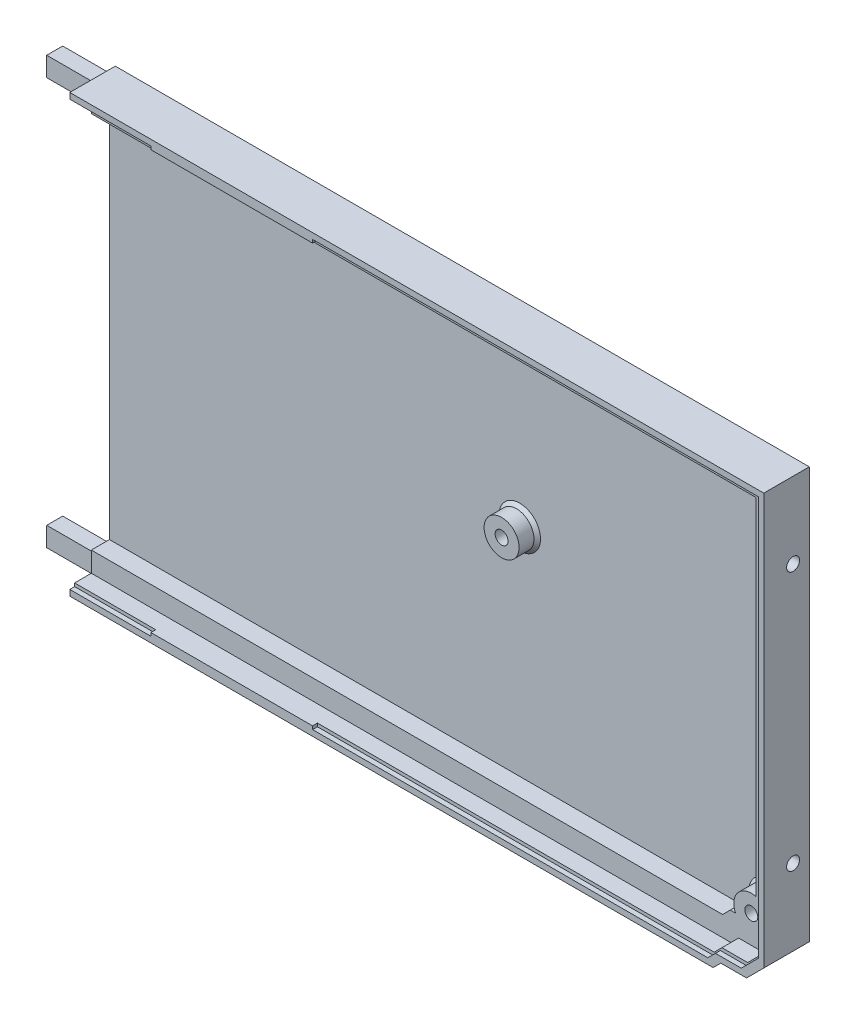
SolidWorks part; units mm, degrees
ref_plane "Přední rovina" through (0, 0, 0) normal (0, 0, 1) x (1, 0, 0)
ref_plane "Horní rovina" through (0, 0, 0) normal (0, 1, 0) x (1, 0, 0)
ref_plane "Pravá rovina" through (0, 0, 0) normal (1, 0, 0) x (0, 0, -1)
sketch "Skica3" plane through (0, 0, 0) normal (0, 0, 1) x (1, 0, 0)
  line L0 (0, 0) -> (415.1053, 0) construction
  line L1 (415.1053, 0) -> (416.6927, -1.5875) construction
  line L2 (416.6927, -1.5875) -> (416.6927, -119.8485) construction
  line L3 (0, 0) -> (-1.5875, -1.5875) construction
  line L4 (-1.5875, -1.5875) -> (-1.5875, -119.8485) construction
  line L5 (-1.5875, -119.8485) -> (0.7934, -122.2292) construction
  line L6 (0.7934, -122.2292) -> (8.7304, -122.2292) construction
  line L7 (8.7304, -122.2292) -> (11.1113, -124.61) construction
  line L8 (11.1113, -124.61) -> (403.9933, -124.61) construction
  line L9 (403.9933, -124.61) -> (406.3744, -122.2294) construction
  line L10 (406.3744, -122.2294) -> (414.3114, -122.2294) construction
  line L11 (416.6927, -119.8485) -> (414.3114, -122.2294) construction
  line L12 (2.4125, -4) -> (412.6927, -4)
  line L13 (412.6927, -4) -> (412.6927, -4)
  line L14 (412.6927, -4) -> (412.6927, -118.1914)
  line L15 (412.6927, -118.1914) -> (412.6547, -118.2294)
  line L16 (404.7177, -118.2294) -> (412.6547, -118.2294)
  line L17 (402.3367, -120.61) -> (404.7177, -118.2294)
  line L18 (12.7681, -120.61) -> (402.3367, -120.61)
  line L19 (10.3872, -118.2292) -> (12.7681, -120.61)
  line L20 (2.4502, -118.2292) -> (10.3872, -118.2292)
  line L21 (2.4125, -118.1915) -> (2.4502, -118.2292)
  line L22 (2.4125, -4) -> (2.4125, -118.1915)
  line L23 (2.4125, -4) -> (2.4125, -4)
  line L24 (-1.5875, -119.8485) -> (415.1053, 0) construction
  line L26 (0, 0) -> (416.6927, -119.8485) construction
  dimension "D1" = 135
  dimension "D2" = 135
  dimension "D3" = 4
  dimension "D4" = 2.245
  dimension "D5" = 2.245
  dimension "D6" = 118.261
  dimension "D7" = 118.261
  dimension "D8" = 3.367
  dimension "D9" = 7.937
  dimension "D10" = 3.367
  dimension "D11" = 392.882
  dimension "D12" = 3.367
  dimension "D13" = 7.937
  dimension "D14" = 3.3674
extrude "Přidat vysunutím1" add sketch "Skica3" along normal blind 5.6
shell "Skořepina1" thickness 1.8 removed face at (207.5525, -95.852, 5.6) outward yes
sketch "Skica7" plane through (0, 0, 5.6) normal (0, 0, 1) x (1, 0, 0)
  line L20 (-6.5875, 5) -> (-6.5875, -121.9196)
  line L21 (-6.5875, -121.9196) -> (-1.2775, -127.2292)
  line L22 (-1.2775, -127.2292) -> (6.6595, -127.2292)
  line L23 (6.6595, -127.2292) -> (9.0403, -129.61)
  line L24 (9.0403, -129.61) -> (406.0641, -129.61)
  line L25 (406.0641, -129.61) -> (408.4452, -127.2294)
  line L26 (408.4452, -127.2294) -> (416.3822, -127.2294)
  line L27 (416.3822, -127.2294) -> (421.6927, -121.9198)
  line L28 (421.6927, -121.9198) -> (421.6927, 5)
  line L29 (421.6927, 5) -> (-6.5875, 5)
  line L30 (-6.5875, 5) -> (-6.5875, -121.9196)
  line L31 (-6.5875, -121.9196) -> (-1.2775, -127.2292)
  line L32 (-1.2775, -127.2292) -> (6.6595, -127.2292)
  line L33 (6.6595, -127.2292) -> (9.0403, -129.61)
  line L34 (9.0403, -129.61) -> (406.0641, -129.61)
  line L35 (406.0641, -129.61) -> (408.4452, -127.2294)
  line L36 (408.4452, -127.2294) -> (416.3822, -127.2294)
  line L37 (416.3822, -127.2294) -> (421.6927, -121.9198)
  line L38 (421.6927, -121.9198) -> (421.6927, 5)
  line L39 (421.6927, 5) -> (-6.5875, 5)
  line L40 (-3.7875, 2.2) -> (-3.7875, -120.7598)
  line L41 (-3.7875, -120.7598) -> (-0.1178, -124.4292)
  line L42 (-0.1178, -124.4292) -> (7.8192, -124.4292)
  line L43 (7.8192, -124.4292) -> (10.2001, -126.81)
  line L44 (10.2001, -126.81) -> (404.9045, -126.81)
  line L45 (404.9045, -126.81) -> (407.2855, -124.4294)
  line L46 (407.2855, -124.4294) -> (415.2225, -124.4294)
  line L47 (415.2225, -124.4294) -> (418.8927, -120.7598)
  line L48 (418.8927, -120.7598) -> (418.8927, 2.2)
  line L49 (418.8927, 2.2) -> (-3.7875, 2.2)
  line L50 (-3.7875, 2.2) -> (-3.7875, -120.7598)
  line L51 (-3.7875, -120.7598) -> (-0.1178, -124.4292)
  line L52 (-0.1178, -124.4292) -> (7.8192, -124.4292)
  line L53 (7.8192, -124.4292) -> (10.2001, -126.81)
  line L54 (10.2001, -126.81) -> (404.9045, -126.81)
  line L55 (404.9045, -126.81) -> (407.2855, -124.4294)
  line L56 (407.2855, -124.4294) -> (415.2225, -124.4294)
  line L57 (415.2225, -124.4294) -> (418.8927, -120.7598)
  line L58 (418.8927, -120.7598) -> (418.8927, 2.2)
  line L59 (418.8927, 2.2) -> (-3.7875, 2.2)
  dimension "D2" = 4.4
  dimension "D1" = 7.2
extrude "Přidat vysunutím3" add sketch "Skica7" along normal blind 5.15 separate body
sketch "Skica8" plane through (0, 0, 5.6) normal (0, 0, -1) x (-1, 0, 0)
  line L0 (-421.6927, 5) -> (6.5875, 5)
  line L1 (6.5875, 5) -> (6.5875, -121.9196)
  line L2 (6.5875, 5) -> (6.5875, -121.9196) construction
  line L3 (6.5875, -121.9196) -> (1.2775, -127.2292)
  line L4 (1.2775, -127.2292) -> (-6.6595, -127.2292)
  line L5 (-6.6595, -127.2292) -> (-9.0403, -129.61)
  line L6 (-9.0403, -129.61) -> (-406.0641, -129.61)
  line L7 (-406.0641, -129.61) -> (-408.4452, -127.2294)
  line L8 (-408.4452, -127.2294) -> (-416.3822, -127.2294)
  line L9 (-416.3822, -127.2294) -> (-421.6927, -121.9198)
  line L10 (-421.6927, -121.9198) -> (-421.6927, 5)
  line L11 (-0.6125, -2.2) -> (-0.6125, -118.9371)
  line L12 (-414.4927, -2.2) -> (-0.6125, -2.2) construction
  line L13 (-0.6125, -2.2) -> (-0.6125, -118.9371) construction
  line L14 (-0.6125, -118.9371) -> (-1.7047, -120.0292)
  line L15 (-1.7047, -120.0292) -> (-9.6417, -120.0292)
  line L16 (-9.6417, -120.0292) -> (-12.0226, -122.41)
  line L17 (-12.0226, -122.41) -> (-403.0822, -122.41)
  line L18 (-403.0822, -122.41) -> (-405.4632, -120.0294)
  line L19 (-405.4632, -120.0294) -> (-413.4002, -120.0294) construction
  line L20 (-405.4632, -120.0294) -> (-413.4002, -120.0294)
  line L21 (-413.4002, -120.0294) -> (-414.4927, -118.9371) construction
  line L22 (-413.4002, -120.0294) -> (-414.4927, -118.9371)
  line L23 (-414.4927, -118.9371) -> (-414.4927, -2.2)
  line L24 (-414.4927, -2.2) -> (-0.6125, -2.2)
extrude "Přidat vysunutím4" add sketch "Skica8" along normal up to surface (7.4 mm away) up to face at (207.5525, -96.7211, -1.8)
sketch "Skica11" plane through (0, 0, 10.75) normal (0, 0, 1) x (1, 0, 0)
  line L0 (207.5526, 3.195) -> (207.5526, 5) construction
  line L1 (421.6927, 5) -> (-6.5875, 5) construction
  line L2 (207.5522, -127.805) -> (207.5522, -129.61) construction
  line L3 (9.0403, -129.61) -> (406.0641, -129.61) construction
  line L4 (-4.9474, -58.4598) -> (-6.5875, -58.4598) construction
  line L5 (-6.5875, 5) -> (-6.5875, -121.9196) construction
  line L6 (420.0526, -58.4599) -> (421.6927, -58.4599) construction
  line L7 (421.6927, -121.9198) -> (421.6927, 5) construction
  line L8 (404.9045, -126.81) -> (407.2855, -124.4294) construction
  line L9 (415.2225, -124.4294) -> (418.8927, -120.7598) construction
  line L10 (7.8192, -124.4292) -> (10.2001, -126.81) construction
  line L11 (-3.7875, -120.7598) -> (-0.1178, -124.4292) construction
  line L13 (407.2855, -124.4294) -> (415.2225, -124.4294) construction
  line L14 (-0.1178, -124.4292) -> (7.8192, -124.4292) construction
  line L30 (420.0526, 3.195) -> (-4.9474, 3.195)
  line L31 (-4.9474, 3.195) -> (-4.9474, -120.1146)
  line L32 (-4.9474, -120.1146) -> (-0.24, -124.8217)
  line L33 (-0.24, -124.8217) -> (7.697, -124.8217)
  line L34 (7.697, -124.8217) -> (10.6804, -127.805)
  line L35 (10.6804, -127.805) -> (404.4241, -127.805)
  line L36 (404.4241, -127.805) -> (406.8051, -125.4244)
  line L37 (406.8051, -125.4244) -> (414.7421, -125.4244)
  line L38 (414.7421, -125.4244) -> (420.0526, -120.1148)
  line L39 (420.0526, -120.1148) -> (420.0526, 3.195)
  line L45 (421.6927, 5) -> (-6.5875, 5)
  line L46 (-6.5875, 5) -> (-6.5875, -121.9196)
  line L47 (-6.5875, -121.9196) -> (-1.2775, -127.2292)
  line L48 (-1.2775, -127.2292) -> (6.6595, -127.2292)
  line L49 (6.6595, -127.2292) -> (9.0403, -129.61)
  line L50 (9.0403, -129.61) -> (406.0641, -129.61)
  line L51 (406.0641, -129.61) -> (408.4452, -127.2294)
  line L52 (408.4452, -127.2294) -> (416.3822, -127.2294)
  line L53 (416.3822, -127.2294) -> (421.6927, -121.9198)
  line L54 (421.6927, -121.9198) -> (421.6927, 5)
  line L55 (421.6927, 5) -> (-6.5875, 5)
  line L56 (-6.5875, 5) -> (-6.5875, -121.9196)
  line L57 (-6.5875, -121.9196) -> (-1.2775, -127.2292)
  line L58 (-1.2775, -127.2292) -> (6.6595, -127.2292)
  line L59 (6.6595, -127.2292) -> (9.0403, -129.61)
  line L60 (9.0403, -129.61) -> (406.0641, -129.61)
  line L61 (406.0641, -129.61) -> (408.4452, -127.2294)
  line L62 (408.4452, -127.2294) -> (416.3822, -127.2294)
  line L63 (416.3822, -127.2294) -> (421.6927, -121.9198)
  line L64 (421.6927, -121.9198) -> (421.6927, 5)
  point P0 (207.5523, -63.11)
  point P2 (207.5523, -63.11)
  dimension "D1" = 131
  dimension "D2" = 425
  dimension "D3" = 0
extrude "Přidat vysunutím5" add sketch "Skica11" along normal blind 1.5
sketch "Skica14" plane through (0, 0, 10.75) normal (0, 0, 1) x (1, 0, 0)
  line L0 (418.8927, 2.2) -> (-3.7875, 2.2) construction
  line L1 (182.5326, 2.2) -> (132.6326, 2.2)
  line L2 (182.5326, 2.2) -> (182.5326, 3.195)
  line L3 (182.5326, 3.195) -> (132.6326, 3.195)
  line L4 (132.6326, 2.2) -> (132.6326, 3.195)
  line L5 (420.0526, 3.195) -> (-4.9474, 3.195) construction
  line L6 (418.8927, 2.2) -> (-3.7875, 2.2) construction
  line L7 (232.5726, 2.2) -> (282.4726, 2.2)
  line L8 (232.5726, 2.2) -> (232.5726, 3.195)
  line L9 (232.5726, 3.195) -> (282.4726, 3.195)
  line L10 (282.4726, 2.2) -> (282.4726, 3.195)
  line L11 (207.5526, 3.195) -> (207.5522, -127.805) construction
  line L12 (10.6804, -127.805) -> (404.4241, -127.805) construction
  line L13 (10.2001, -126.81) -> (404.9045, -126.81) construction
  line L14 (232.5722, -126.81) -> (282.4722, -126.81)
  line L15 (232.5722, -126.81) -> (232.5722, -127.805)
  line L16 (232.5722, -127.805) -> (282.4722, -127.805)
  line L17 (282.4722, -126.81) -> (282.4722, -127.805)
  line L18 (10.6804, -127.805) -> (404.4241, -127.805) construction
  line L20 (182.5322, -126.81) -> (132.6322, -126.81)
  line L21 (182.5322, -126.81) -> (182.5322, -127.805)
  line L22 (182.5322, -127.805) -> (132.6322, -127.805)
  line L23 (132.6322, -126.81) -> (132.6322, -127.805)
  dimension "D1" = 49.9
  dimension "D2" = 49.9
  dimension "D3" = 25.02
  dimension "D4" = 25.02
  dimension "D5" = 49.9
  dimension "D6" = 49.9
  dimension "D7" = 25.02
  dimension "D8" = 25.02
extrude "Přidat vysunutím6" add sketch "Skica14" along normal up to surface (1.5 mm away) up to face at (207.5524, -100.1977, 12.25)
sketch "Skica15" plane through (0, 0, 0) normal (0, 0, 1) x (1, 0, 0)
  line L1 (34.9015, 4.5) -> (37.9015, 4.5)
  line L2 (34.9015, 4.5) -> (34.9015, -4.5)
  line L3 (34.9015, -4.5) -> (37.9015, -4.5)
  line L4 (37.9015, 4.5) -> (37.9015, -4.5)
  line L5 (34.9015, 4.5) -> (37.9015, -4.5) construction
  line L6 (34.9015, -4.5) -> (37.9015, 4.5) construction
  line L20 (-1.5875, 0) -> (-1.5875, -119.8485)
  line L21 (-1.5875, -119.8485) -> (0.7934, -122.2292)
  line L22 (0.7934, -122.2292) -> (8.7304, -122.2292)
  line L23 (8.7304, -122.2292) -> (11.1113, -124.61)
  line L24 (11.1113, -124.61) -> (403.9933, -124.61)
  line L25 (403.9933, -124.61) -> (406.3744, -122.2294)
  line L26 (406.3744, -122.2294) -> (414.3114, -122.2294)
  line L27 (414.3114, -122.2294) -> (416.6927, -119.8485)
  line L28 (416.6927, -119.8485) -> (416.6927, 0)
  line L29 (416.6927, 0) -> (-1.5875, 0)
  line L30 (-1.5875, 0) -> (-1.5875, -119.8485) construction
  line L31 (-1.5875, -119.8485) -> (0.7934, -122.2292) construction
  line L32 (0.7934, -122.2292) -> (8.7304, -122.2292) construction
  line L33 (8.7304, -122.2292) -> (11.1113, -124.61) construction
  line L34 (11.1113, -124.61) -> (403.9933, -124.61) construction
  line L35 (403.9933, -124.61) -> (406.3744, -122.2294) construction
  line L36 (406.3744, -122.2294) -> (414.3114, -122.2294) construction
  line L37 (414.3114, -122.2294) -> (416.6927, -119.8485) construction
  line L38 (416.6927, -119.8485) -> (416.6927, 0) construction
  line L39 (416.6927, 0) -> (-1.5875, 0) construction
  circle A0 centre (3.9685, -115.9542) radius 5.4
  circle A1 centre (33.4915, -69.051) radius 5.4
  circle A2 centre (411.1977, -115.8794) radius 5.4
  circle A3 centre (334.1477, -53.972) radius 5.4
  point P2 (-1.4315, -115.9542)
  point P3 (3.9685, -121.3542)
  point P4 (28.0915, -69.051)
  point P8 (33.4915, -74.451)
  point P12 (411.1977, -121.2794)
  point P13 (416.5977, -115.8794)
  point P17 (334.1477, -48.572)
  point P19 (339.5477, -53.972)
  point P21 (36.4015, 0)
  point P23 (36.4015, 0)
  dimension "D2" = 0.156
  dimension "D4" = 10.8
  dimension "D7" = 10.8
  dimension "D10" = 10.8
  dimension "D13" = 10.8
  dimension "D3" = 0.875
  dimension "D5" = 29.679
  dimension "D6" = 50.159
  dimension "D8" = 0.095
  dimension "D9" = 0.95
  dimension "D11" = 77.145
  dimension "D12" = 48.572
  dimension "D14" = 37.989
  dimension "D15" = 9
  dimension "D16" = 3
  dimension "D1" = 4
extrude "Přidat vysunutím7" add sketch "Skica15" along normal blind 5.6
sketch "Skica16" plane through (0, 0, 5.6) normal (0, 0, 1) x (1, 0, 0)
  circle A0 centre (3.9685, -115.9542) radius 2
  circle A1 centre (33.4915, -69.051) radius 2
  circle A2 centre (334.1477, -53.972) radius 2
  circle A3 centre (411.1977, -115.8794) radius 2
  dimension "D1" = 4
  dimension "D2" = 4
  dimension "D3" = 4
  dimension "D4" = 4
extrude "Odebrat vysunutím1" cut sketch "Skica16" against normal blind 5.75
chamfer "Zkosení1" distance 1 angle 45 4 edges at (407.0694, -112.3984, 0) (8.0492, -112.4175, 0) (38.8915, -69.051, 0) (339.5477, -53.972, 0)
sketch "Skica17" plane through (0, 0, 5.6) normal (0, 0, 1) x (1, 0, 0)
  line L0 (34.9015, -4.5) -> (37.9015, -4.5) construction
  line L1 (24.4015, -11.2) -> (48.4015, -11.2)
  line L2 (24.4015, -11.2) -> (24.4015, 2.2)
  line L3 (24.4015, 2.2) -> (48.4015, 2.2)
  line L4 (48.4015, -11.2) -> (48.4015, 2.2)
  line L5 (24.4015, -11.2) -> (48.4015, 2.2) construction
  line L6 (24.4015, 2.2) -> (48.4015, -11.2) construction
  line L7 (418.8927, 2.2) -> (-3.7875, 2.2) construction
  point P0 (36.4015, -4.5)
  dimension "D1" = 24
extrude "Odebrat vysunutím2" cut sketch "Skica17" against normal blind 1.6
sketch "Skica18" plane through (0, -4.5, 0) normal (0, -1, 0) x (1, 0, 0)
  line L0 (33.6515, 4) -> (39.1515, 4) construction
  line L1 (37.9015, 4) -> (34.9015, 4) construction
  line L2 (37.9015, 4) -> (48.4015, 4) construction
  line L3 (33.6515, 7.5) -> (39.1515, 7.5)
  line L4 (33.6515, 0.5) -> (39.1515, 0.5)
  arc A0 (33.6515, 7.5) -> (33.6515, 0.5) centre (33.6515, 4) ccw
  arc A1 (39.1515, 0.5) -> (39.1515, 7.5) centre (39.1515, 4) ccw
  point P6 (36.4015, 4)
  point P11 (30.1515, 4)
  point P12 (42.6515, 4)
  dimension "D1" = 12.5
  dimension "D2" = 7
extrude "Odebrat vysunutím3" cut sketch "Skica18" against normal up to surface (9.5 mm away) up to face at (207.5526, 5, 5.225)
sketch "Skica23" plane through (-6.5875, 0, 0) normal (-1, 0, 0) x (0, 0, 1)
  line L2 (-1.8, 5) -> (-1.8, -121.9196) construction
  line L4 (-1.8, -58.4598) -> (12.25, -58.4598) construction
  line L5 (12.25, 5) -> (12.25, -121.9196) construction
  circle A0 centre (3.2, -18.4598) radius 2
  circle A1 centre (3.2, -98.4598) radius 2
  point P8 (-1.8, -58.4598)
  dimension "D2" = 4
  dimension "D3" = 4
  dimension "D1" = 40
  dimension "D4" = 5
extrude "Odebrat vysunutím4" cut sketch "Skica23" against normal blind 5.7
sketch "Skica24" plane through (421.6927, 0, 0) normal (1, 0, 0) x (0, 0, -1)
  line L0 (1.8, -58.4599) -> (-12.25, -58.4599) construction
  line L1 (1.8, -121.9198) -> (1.8, 5) construction
  line L2 (-12.25, -121.9198) -> (-12.25, 5) construction
  circle A0 centre (-3.2, -18.4599) radius 2
  circle A1 centre (-3.2, -98.4599) radius 2
  dimension "D1" = 4
  dimension "D2" = 4
  dimension "D3" = 40
  dimension "D4" = 5
extrude "Odebrat vysunutím5" cut sketch "Skica24" against normal blind 5.7
sketch "Skica25" plane through (0, 0, -1.8) normal (0, 0, -1) x (-1, 0, 0)
  line L0 (-421.6927, -121.9198) -> (-421.6927, 5) construction
  line L1 (-421.6927, 5) -> (6.5875, 5) construction
  line L2 (6.5875, 5) -> (6.5875, -121.9196) construction
  line L3 (-9.0403, -129.61) -> (-406.0641, -129.61) construction
  circle A0 centre (-401.6927, -15) radius 6.25
  circle A1 centre (-13.4125, -15) radius 6.25
  circle A2 centre (-388.4452, -109.61) radius 6.25
  circle A3 centre (-26.6595, -109.61) radius 6.25
  dimension "D1" = 12.5
  dimension "D2" = 12.5
  dimension "D3" = 12.5
  dimension "D4" = 12.5
  dimension "D5" = 20
  dimension "D6" = 20
  dimension "D7" = 20
  dimension "D8" = 20
  dimension "D9" = 20
  dimension "D10" = 20
  dimension "D11" = 20
  dimension "D12" = 20
extrude "Odebrat vysunutím6" cut sketch "Skica25" against normal blind 1.5
sketch "Skica26" plane through (0, 5, 0) normal (0, 1, 0) x (1, 0, 0)
  line L0 (421.6927, -12.25) -> (-6.5875, -12.25) construction
  line L1 (207.5526, -12.25) -> (-6.5875, -12.25)
  line L2 (207.5526, -12.25) -> (207.5526, 1.8)
  line L3 (207.5526, 1.8) -> (-6.5875, 1.8)
  line L4 (-6.5875, -12.25) -> (-6.5875, 1.8)
extrude "Odebrat vysunutím7" cut sketch "Skica26" against normal through all
sketch "Skica27" plane through (207.5526, 0, 0) normal (-1, 0, 0) x (0, 0, 1)
  line L0 (0, -4) -> (-1.8, -4) construction
  line L1 (-1.8, -129.61) -> (-1.8, 5) construction
  line L2 (-1.8, -4) -> (5.6, 5) construction
  line L3 (12.25, 5) -> (-1.8, 5) construction
  line L4 (5.6, 5) -> (5.6, 2.2) construction
  line L5 (-1.8, 5) -> (5.6, -4) construction
  line L6 (0, -120.61) -> (-1.8, -120.61) construction
  line L7 (-0.5667, -2.5) -> (4.3667, -2.5)
  line L8 (-0.5667, -2.5) -> (-0.5667, 3.5)
  line L9 (-0.5667, 3.5) -> (4.3667, 3.5)
  line L10 (4.3667, -2.5) -> (4.3667, 3.5)
  line L11 (-0.5667, -2.5) -> (4.3667, 3.5) construction
  line L12 (-0.5667, 3.5) -> (4.3667, -2.5) construction
  line L13 (5.6, -126.81) -> (5.6, -129.61) construction
  line L14 (12.25, -129.61) -> (-1.8, -129.61) construction
  line L15 (-1.8, -120.61) -> (5.6, -129.61) construction
  line L16 (-1.8, -129.61) -> (5.6, -120.61) construction
  line L17 (5.6, -120.61) -> (0, -120.61) construction
  line L18 (-0.5667, -128.11) -> (4.3667, -128.11)
  line L19 (-0.5667, -128.11) -> (-0.5667, -122.11)
  line L20 (-0.5667, -122.11) -> (4.3667, -122.11)
  line L21 (4.3667, -128.11) -> (4.3667, -122.11)
  line L22 (-0.5667, -128.11) -> (4.3667, -122.11) construction
  line L23 (-0.5667, -122.11) -> (4.3667, -128.11) construction
  point P14 (1.9, 0.5)
  point P31 (1.9, -125.11)
  dimension "D1" = 1.5
  dimension "D2" = 1.5
extrude "Přidat vysunutím8" add sketch "Skica27" along normal blind 15
